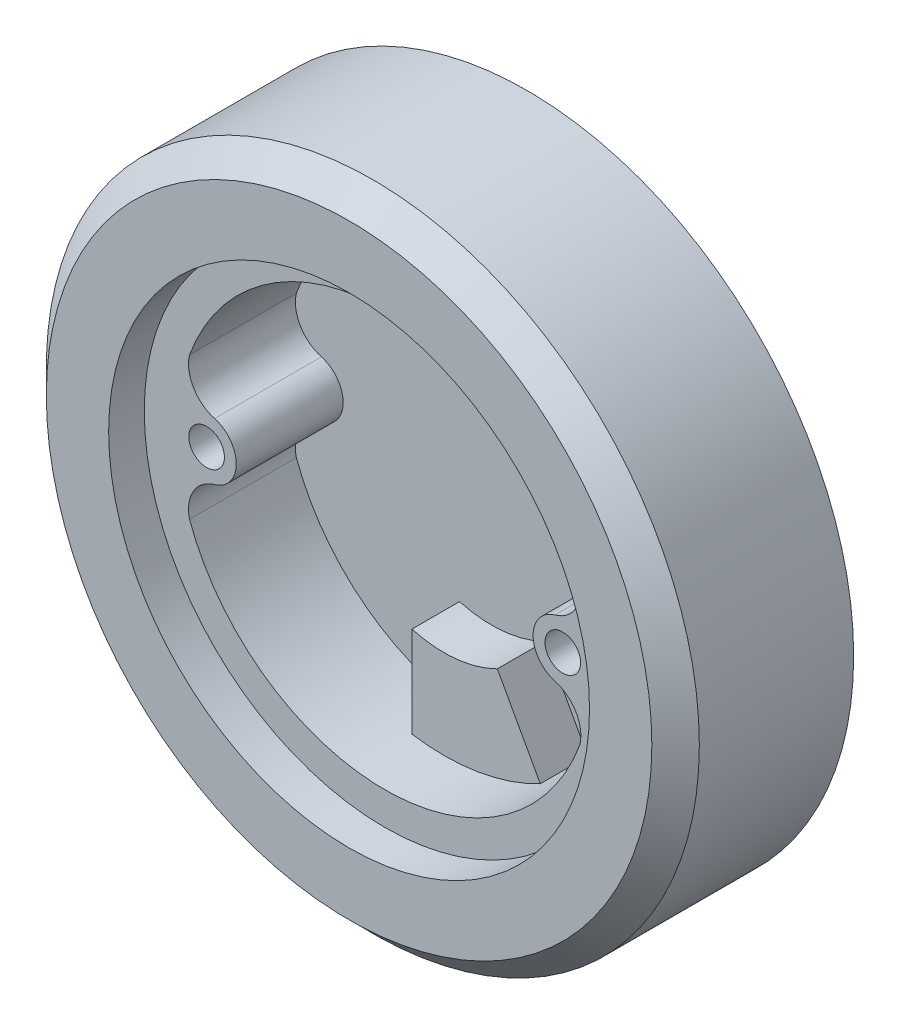
SolidWorks part; units mm, degrees
ref_plane "Front Plane" through (0, 0, 0) normal (0, 0, 1) x (1, 0, 0)
ref_plane "Top Plane" through (0, 0, 0) normal (0, 1, 0) x (1, 0, 0)
ref_plane "Right Plane" through (0, 0, 0) normal (1, 0, 0) x (0, 0, -1)
sketch "Sketch1" plane through (0, 0, 0) normal (0, 0, 1) x (1, 0, 0)
  circle A0 centre (0, 0) radius 27.5
  dimension "D1" = 55
extrude "Boss-Extrude1" add sketch "Sketch1" along normal blind 15
chamfer "Chamfer1" distance 2 angle 45 1 edges at (27.5, 0, 15)
sketch "Sketch2" plane through (0, 0, 15) normal (0, 0, 1) x (1, 0, 0)
  circle A0 centre (0, 0) radius 17.5
  dimension "D1" = 35
extrude "Cut-Extrude1" cut sketch "Sketch2" against normal blind 12
sketch "Sketch3" plane through (0, 0, 15) normal (0, 0, 1) x (1, 0, 0)
  circle A0 centre (0, 0) radius 20.25
  dimension "D1" = 40.5
extrude "Cut-Extrude2" cut sketch "Sketch3" against normal blind 3
sketch "Sketch4" plane through (0, 0, 0) normal (0, 1, 0) x (1, 0, 0)
  line L0 (-17.5, -3) -> (17.5, -3) construction
  circle A0 centre (0, -5) radius 2
  dimension "D1" = 4
  dimension "D2" = 2
extrude "Cut-Extrude3" cut sketch "Sketch4" against normal through all contours A0
sketch "Sketch5" plane through (0, 0, 12) normal (0, 0, 1) x (1, 0, 0)
  line L0 (8.25, 0) -> (-8.25, 0) construction
  line L1 (-17.0821, 0) -> (-9.1931, 0) construction
  arc A0 (-14.3285, -2.4081) -> (-14.3285, 2.4081) centre (-15, 0) ccw
  arc A1 (-14.3285, -2.4081) -> (-16.4393, -6) centre (-13.5226, -5.2979) ccw
  circle A2 centre (0, 0) radius 17.5 construction
  arc A3 (-14.3285, 2.4081) -> (-16.4393, 6) centre (-13.5226, 5.2979) cw
  arc A4 (-16.4393, -6) -> (-16.4393, 6) centre (0, 0) cw
  dimension "D1" = 5
  dimension "D4" = 3
  dimension "D2" = 15
  dimension "D3" = 6
extrude "Boss-Extrude2" add sketch "Sketch5" against normal up to surface (9 mm away) up to face at (17.5, 0, 3)
sketch "Sketch6" plane through (0, 0, 12) normal (0, 0, 1) x (1, 0, 0)
  circle A0 centre (-15, 0) radius 1.5
  dimension "D1" = 3
extrude "Cut-Extrude4" cut sketch "Sketch6" against normal through all
chamfer "Chamfer2" distance 2 angle 45 1 edges at (-13.5, 0, 0)
mirror "Mirror1" about plane through (0, 0, 0) normal (1, 0, 0) of "Chamfer2", "Boss-Extrude2", "Cut-Extrude4"
sketch "Sketch8" plane through (0, 0, 3) normal (0, 0, 1) x (1, 0, 0)
  line L0 (0, -17.5) -> (0, 0) construction
  line L2 (-2.6967, -17.291) -> (-2.6967, -9.6295)
  line L4 (4.4954, -8.9326) -> (8.1141, -15.5052) construction
  line L5 (8.1141, -15.5052) -> (4.4954, -8.9326)
  arc A0 (-2.6967, -17.291) -> (8.1141, -15.5052) centre (0, 0) ccw
  arc A1 (-16.4393, -6) -> (0, -17.5) centre (0, 0) ccw construction
  arc A2 (-2.6967, -9.6295) -> (4.4954, -8.9326) centre (0, 0) ccw
  point P2 (0, 0)
  point P5 (0, 0)
  dimension "D3" = 10
extrude "Boss-Extrude8" add sketch "Sketch8" along normal blind 4.01
ref_plane "Plane1" through (0, 0, 5.01) normal (0, 0, 1) x (1, 0, 0)
ref_axis "Axis1" [suppressed] through (0, 30.25, 7.01) along (0, -1, 0)
sketch "Sketch10" plane through (0, 0, 5.01) normal (0, 0, 1) x (1, 0, 0)
  line L0 (0, -29.9582) -> (0, -15.8745) construction
  arc A1 (1.75, -13.8902) -> (9.4717, -10.3096) centre (0, 0) ccw construction
  arc A2 (1.75, -13.8902) -> (0, -15.8745) centre (2, -15.8745) ccw construction
  point P0 (5.8896, -12.7009)
  point P2 (0, -29.9582)
  point P3 (9.4717, -10.3096)
  point P4 (1.75, -13.8902)
  point P11 (0, -15.8745)
  point P12 (0, -15.8745)
  dimension "D1" = 2
  dimension "D2" = 14
sketch "Sketch13" plane through (-0.3243, -0.1785, 0) normal (0.876, 0.4823, 0) x (0, 0, -1)
  line L0 (-3, -17.4961) -> (-3, -9.9931) construction
  line L1 (-5, -16) -> (-7.01, -16)
  line L2 (-7.01, -17.4961) -> (-7.01, -9.9931) construction
  line L3 (-7.01, -16) -> (-7.01, -12)
  line L4 (-7.01, -12) -> (-5, -12)
  arc A0 (-5, -16) -> (-5, -12) centre (-5, -14) ccw
  dimension "D1" = 14
  dimension "D2" = 4
  dimension "D3" = 2
